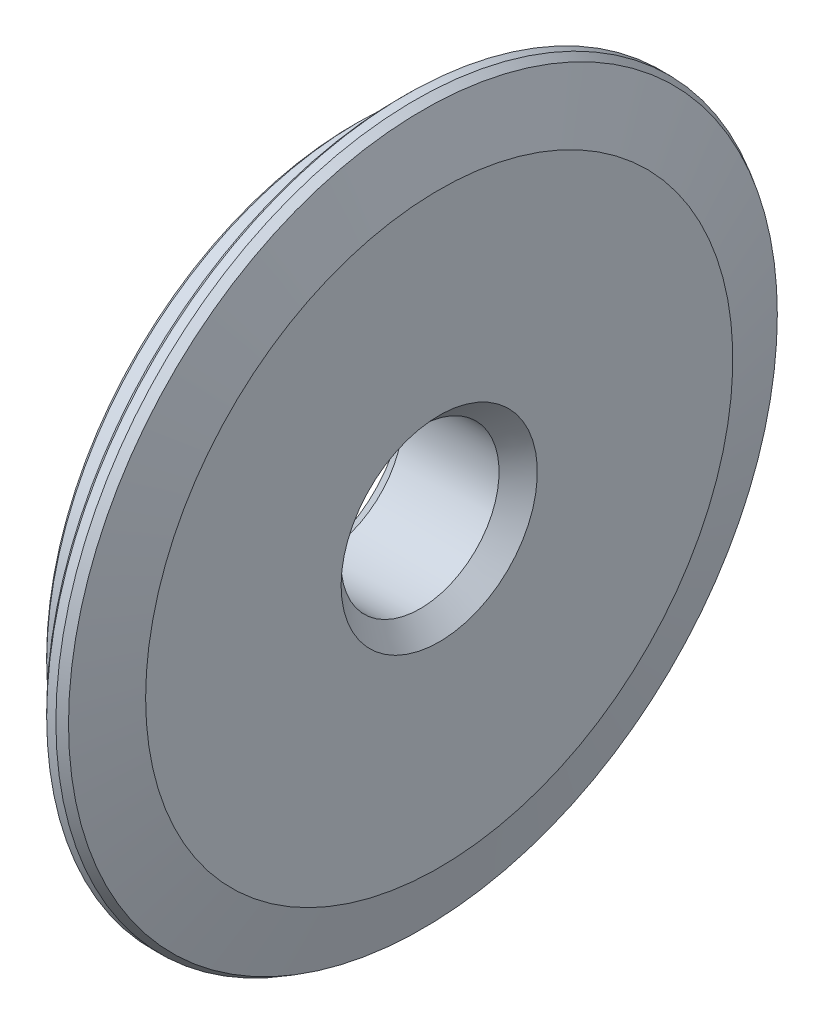
SolidWorks part; units mm, degrees
material "Сталь 40Х ГОСТ 4543-71"
ref_plane "Спереди (Плоскость XY)" through (0, 0, 0) normal (0, 0, 1) x (1, 0, 0)
ref_plane "Сверху (Плоскость XZ)" through (0, 0, 0) normal (0, 1, 0) x (1, 0, 0)
ref_plane "Справа (Плоскость ZY)" through (0, 0, 0) normal (1, 0, 0) x (0, 0, -1)
other "Configuration Table"
sketch "Эскиз1" plane through (0, 0, 0) normal (0, 0, 1) x (1, 0, 0)
  line L0 (0, 0) -> (129.3383, 0) construction
  line L1 (0, 8.25) -> (14, 8.25)
  line L2 (14, 8.25) -> (14, 30.664)
  line L3 (14, 30.664) -> (12.1683, 37.5)
  line L4 (12.1683, 37.5) -> (10, 37.5)
  line L5 (10, 37.5) -> (10, 32.5)
  line L6 (10, 32.5) -> (5, 32.5)
  line L7 (5, 32.5) -> (5, 30.5)
  line L8 (5, 30.5) -> (11, 30.5)
  line L9 (11, 30.5) -> (11, 12.5)
  line L10 (11, 12.5) -> (0, 12.5)
  line L11 (0, 12.5) -> (0, 8.25)
  line L12 (0, 0) -> (0, -53.2012) construction
  point P5 (0, 0)
  dimension "D1" = 16.5
  dimension "D2" = 61
  dimension "D3" = 11
  dimension "D4" = 3
  dimension "D5" = 65
  dimension "D6" = 25
  dimension "D7" = 10
  dimension "D8" = 6
  dimension "D9" = 75
  dimension "D10" = 15
  dimension "D11" = 0
  dimension "D12" = 30.664
revolve "Повернуть1" add sketch "Эскиз1" angle 360 about L0
cosmetic thread "Условное изображение резьбы1" parameters "D2"=18
chamfer "Фаска1" distance 2 angle 45 2 edges at (14, 0, 8.25) (0, 0, 8.25)
chamfer "Фаска2" distance 0.5 angle 45 4 edges at (12.1683, 0, 37.5) (10, 0, 37.5) (5, 0, 30.5) (5, 0, 32.5) first distance on face at (12.1683, 0, 37.5) first distance on face at (10, 0, 37.5) first distance on face at (11, 0, 30.5) first distance on face at (5, 0, 32.5)
